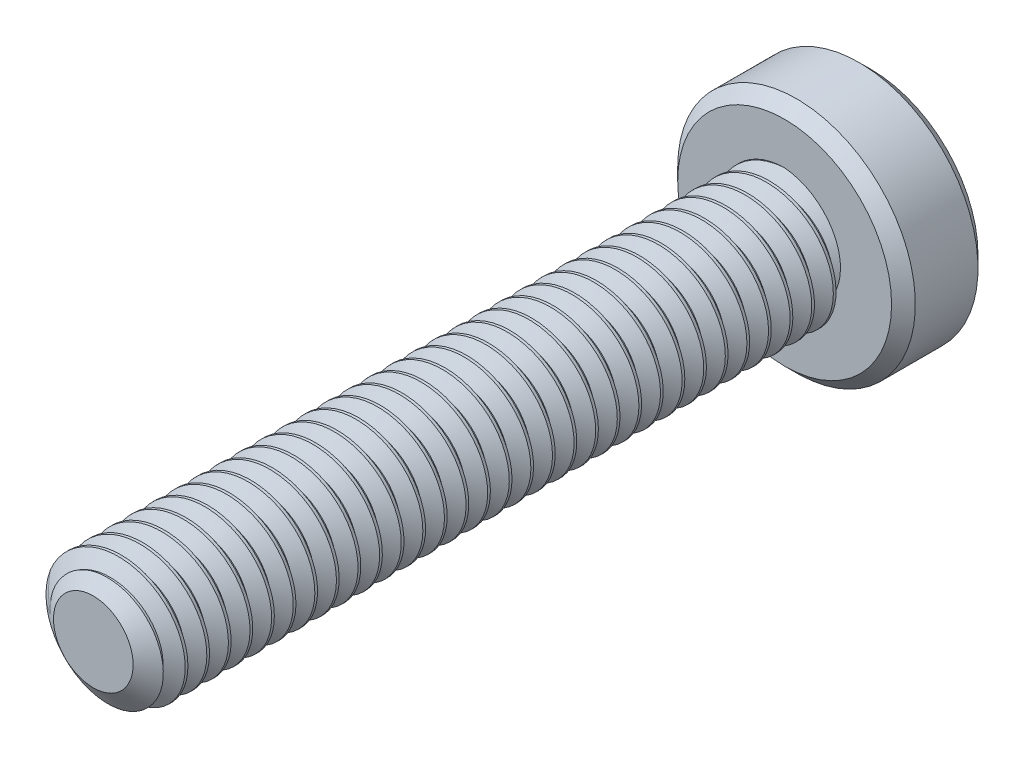
SolidWorks part; units mm, degrees
other "DetailItem1"
ref_plane "Front Plane" through (0, 0, 0) normal (0, 0, 1) x (1, 0, 0)
ref_plane "Top Plane" through (0, 0, 0) normal (0, 1, 0) x (1, 0, 0)
ref_plane "Right Plane" through (0, 0, 0) normal (1, 0, 0) x (0, 0, -1)
sketch "Sketch1" plane through (0, 0, 0) normal (0, 0, 1) x (1, 0, 0)
  circle A0 centre (0, 0) radius 1.5
  dimension "OD" = 3
extrude "Extrude1" add sketch "Sketch1" against normal blind 16
sketch "Sketch2" plane through (0, 0, 0) normal (0, 0, 1) x (1, 0, 0)
  circle A0 centre (0, 0) radius 1.5 construction
  circle A1 centre (0, 0) radius 1.5
curve "Helix/Spiral1" pitch 0.5 height 16.5 turns 33 parameters "pitch"=0.5
sketch "Sketch3" plane through (0, 0, 0) normal (1, 0, 0) x (0, 0, -1)
  line L0 (-0.4375, 1.5) -> (-0.25, 1.1752)
  line L1 (-0.25, 1.1752) -> (-0.1875, 1.1752)
  line L2 (-0.1875, 1.1752) -> (0, 1.5)
  line L3 (-0.4375, 1.5) -> (0, 1.5)
  line L4 (-0.2188, 1.5) -> (-0.2188, 1.1752) construction
  line L5 (-0.3438, 1.3376) -> (-0.0938, 1.3376) construction
  line L6 (0, 1.5) -> (0, -1.5) construction
  dimension "D1" = 0.0625
  dimension "D2" = 0.25
  dimension "D3" = 60
sweep "Cut-Sweep1" cut profiles "Sketch3" path "Helix/Spiral1"
sketch "Sketch4" plane through (0, 0, 0) normal (1, 0, 0) x (0, 0, -1)
  line L0 (0.4053, 1.5) -> (0, 0.9212)
  line L1 (0, 0.9212) -> (0, 1.5)
  line L2 (0.4053, 1.5) -> (0, 1.5)
  line L3 (-0.4375, 1.5) -> (0, 1.5) construction
  line L4 (0, 0) -> (7.0209, 0) construction
  dimension "D1" = 55
  dimension "D2" = 0.254
revolve "Cut-Revolve1" cut sketch "Sketch4" angle 360 about L4
sketch "Sketch6" plane through (0, 0, -16) normal (0, 0, -1) x (-1, 0, 0)
  circle A0 centre (0, 0) radius 2.75
  dimension "head dia" = 5.5
extrude "Extrude2" add sketch "Sketch6" along normal blind 2
sketch "Sketch7" plane through (0, 0, -18) normal (0, 0, -1) x (-1, 0, 0)
  line L1 (0, 1.1547) -> (-1, 0.5774)
  line L2 (-1, 0.5774) -> (-1, -0.5774)
  line L3 (-1, -0.5774) -> (0, -1.1547)
  line L4 (0, -1.1547) -> (1, -0.5774)
  line L5 (1, -0.5774) -> (1, 0.5774)
  line L6 (1, 0.5774) -> (0, 1.1547)
  circle A0 centre (0, 0) radius 1 construction
  dimension "hex dia" = 2
extrude "Cut-Extrude1" cut sketch "Sketch7" against normal blind 1.5
sketch "Sketch8" plane through (0, 0, -18) normal (0, 0, -1) x (-1, 0, 0)
  circle A0 centre (0, 0) radius 1.1547
extrude "Cut-Extrude2" cut sketch "Sketch8" against normal through all draft 45
chamfer "Chamfer1" distance 0.275 angle 45 2 edges at (-2.75, 0, -18) (-2.75, 0, -16)
sketch "Sketch10" plane through (0, 0, -16) normal (0, 0, 1) x (1, 0, 0)
  circle A1 centre (0, 0) radius 1.5
  circle A2 centre (0, 0) radius 1.5
  dimension "D1" = 0
ref_plane "Plane1" through (0, 0, -30) normal (0, 0, 1) x (1, 0, 0)
extrude "partial thread" [suppressed] add sketch "Sketch10" along normal up to surface (20 mm away) separate body
chamfer "Chamfer2" [suppressed] distance 0.06 angle 45
combine bodies "Combine1" [suppressed] operation type add bodies to combine 107 108
sketch "Sketch9" plane through (0, 0, 0) normal (1, 0, 0) x (0, 0, -1)
  line L0 (0, 1.5) -> (0, -1.5) construction
  line L1 (1.25, 1.5) -> (1.25, -1.5) construction
  dimension "D1" = 1.25
equation "\"D3@Helix/Spiral1\" = \"screw length@Extrude1\"+\"pitch@Helix/Spiral1\""
equation "\"D1@Sketch3\" = \"pitch@Helix/Spiral1\"*.125"
equation "\"D2@Sketch3\" = \"pitch@Helix/Spiral1\"*.5"
equation "\"D1@Cut-Extrude1\" = \"hex dia@Sketch7\"*.75"
equation "\"D1@Chamfer1\" = \"head dia@Sketch6\"*.05"
equation "\"D1@Sketch9\" = \"pitch@Helix/Spiral1\"*2.5"
equation "\"D1@Chamfer2\"=\"OD@Sketch1\"*.02"
